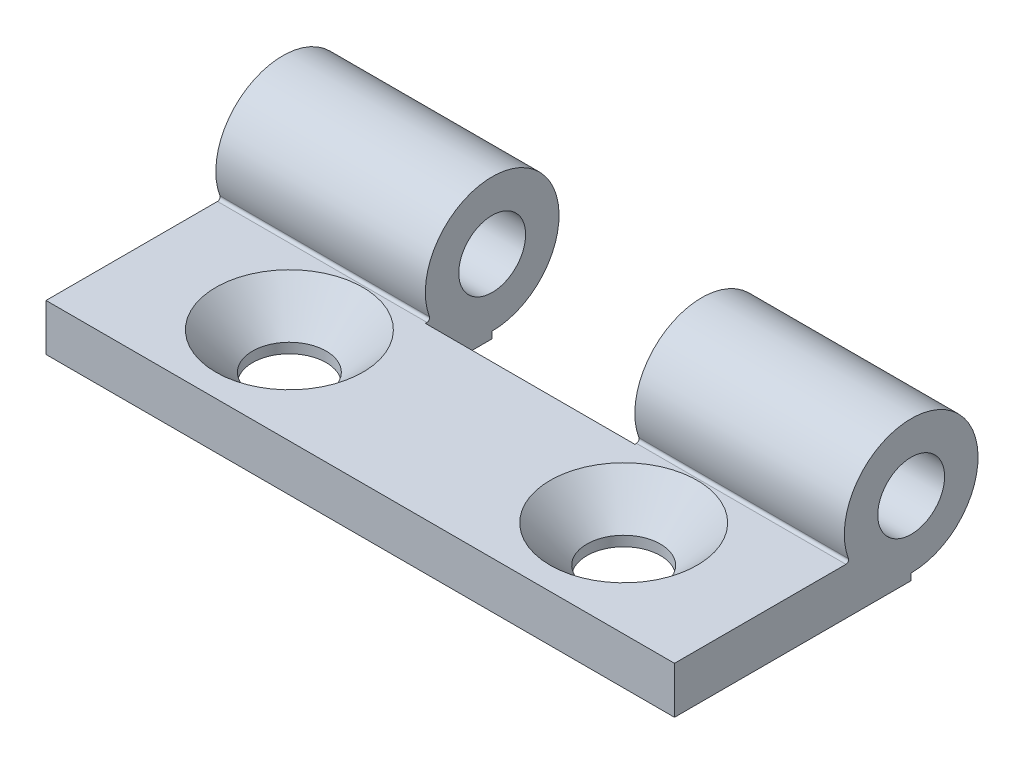
SolidWorks part; units mm, degrees
note: '?' marks a value the reader was unsure of.
ref_plane "Front Plane" through (0, 0, 0) normal (0, 0, 1) x (1, 0, 0)
ref_plane "Top Plane" through (0, 0, 0) normal (0, 1, 0) x (1, 0, 0)
ref_plane "Right Plane" through (0, 0, 0) normal (1, 0, 0) x (0, 0, -1)
ref_axis "Axis_X" through (-13.35, 0, 0) along (1, 0, 0)?
ref_axis "Axis_Y" through (0, 11.025, 0) along (0, -1, 0)?
ref_axis "Axis_Z" through (0, 0, 4.365) along (0, 0, 1)?
ref_plane "K" through (-11, 0, 0) normal (1, 0, 0) x (0, 0, -1)
ref_plane "L" through (36, 0, 0) normal (1, 0, 0) x (0, 0, -1)
sketch "Sketch1" plane through (0, 0, 0) normal (1, 0, 0) x (0, 0, -1)
  line L0 (-28.2, 0) -> (-10.5, 0)
  line L1 (-21, 3.5) -> (-21, 0) construction
  line L2 (7.2, 3.5) -> (7.2, 0) construction
  line L7 (-28.2, 3.5) -> (-15.0826, 3.5)
  line L8 (-28.2, 0) -> (-28.2, 3.5)
  line L12 (-10.5, 0.5) -> (-10.5, 0)
  circle A0 centre (-10.5, 5.5) radius 2.5
  arc A2 (-15.0826, 3.5) -> (-10.5, 0.5) centre (-10.5, 5.5) cw
  dimension "FIX_11" = 5
  dimension "R" = 5
  dimension "T" = 3.5
  dimension "KSS_2" = 17.7
  dimension "E" = 5.5
  dimension "S" = 21
  dimension "J" = 7.2
  dimension "W" = 35.4
extrude "Boss-Extrude1" add sketch "Sketch1" along normal up to surface (36 mm away) and the other way up to surface (11 mm away) up to plane "L" other way up to plane "K"
fillet "Fillet1" radius 0.2 1 edges at (12.5, 3.5, 15.0826)
sketch "Sketch2" plane through (0, 0, 0) normal (0, 1, 0) x (1, 0, 0)
  line L0 (-11, -15.3785) -> (-11, -28.2) construction
  line L1 (4.6667, -5.5) -> (20.3333, -5.5)
  line L2 (4.6667, -5.5) -> (4.6667, -15.5)
  line L3 (4.6667, -15.5) -> (20.3333, -15.5)
  line L4 (20.3333, -5.5) -> (20.3333, -15.5)
  line L6 (36, -5.5) -> (51.6667, -5.5)
  line L7 (36, -5.5) -> (36, -15.5)
  line L8 (36, -15.5) -> (51.6667, -15.5)
  line L9 (51.6667, -5.5) -> (51.6667, -15.5)
  dimension "KSS_3" = 10
  dimension "KSS_4" = 5
  dimension "KSS_11" = 15.6667
  dimension "KSS_12" = 15.6667
  dimension "KSS_10" = 15.6667
extrude "Cut-Extrude1" cut sketch "Sketch2" along normal through all
hole_wizard "CSK1" positions "Sketch4" profile "Sketch3" countersink size "M5" standard "JIS" end condition through all
sketch "Sketch4" plane through (0, 3.5, 0) normal (0, 1, 0) x (1, 0, 0)
  line L0 (0, -28.2) -> (0, -15.0826) construction
  line L1 (0, -28.2) -> (0, -10.5) construction
  point P0 (0, -21)
  point P11 (25, -21)
  dimension "P" = 25
sketch "Sketch3" plane through (0, 3.5, 21) normal (1, 0, 0) x (0, 0, 1)
  line L0 (0, 0) -> (0, 3.5001)
  line L1 (0, 3.5001) -> (2.75, 3.5001)
  line L2 (2.75, 3.5001) -> (2.75, 2.75)
  line L3 (2.75, 2.75) -> (5.5, 0)
  line L5 (5.5, 0) -> (0, 0)
  line L6 (-2.75, 2.75) -> (-5.5, 0) construction
  line L11 (0, -6.35) -> (0, 107.95) construction
  dimension "N_2" = 5.5
  dimension "Thru Hole Depth" = 3.5001
  dimension "N_1" = 11
  dimension "Near C'Sink Angle" = 90
hole_wizard "CSK2" [suppressed] positions "Sketch6" profile "Sketch5" countersink size "M5" standard "JIS"
sketch "Sketch6" plane through (0, 3.5, 0) normal (0, 1, 0) x (1, 0, 0)
  line L7 (25, -15.5) -> (25, -28.2) construction
  line L9 (36, -28.2) -> (-11, -28.2) construction
  point P0 (0, -21)
  point P2 (25, -21)
  point P4 (50, -21)
  dimension "P" = 25
sketch "Sketch5" plane through (0, 3.5, 21) normal (1, 0, 0) x (0, 0, 1)
  line L0 (0, 0) -> (0, 5.1524)
  line L1 (0, 5.1524) -> (2.75, 3.5)
  line L2 (2.75, 3.5) -> (2.75, 2.75)
  line L3 (2.75, 2.75) -> (5.5, 0)
  line L5 (5.5, 0) -> (0, 0)
  line L6 (-2.75, 2.75) -> (-5.5, 0) construction
  line L10 (0, 5.1524) -> (-2.75, 3.5) construction
  line L11 (0, -6.35) -> (0, 107.95) construction
  dimension "N_2" = 5.5
  dimension "Hole Depth" = 3.5
  dimension "N_1" = 11
  dimension "Near C'Sink Angle" = 90
  dimension "Drill Angle" = 118
equation "\"Factor\"= 1.082532"
equation "\"W\"=35.4"
equation "\"KSS_2@Sketch1\"=\"W@Sketch1\"/2"
equation "\"KSS_3\"= if ( \"W\" = 35.4 , 10 , 11 )"
equation "\"KSS_4\"= if ( \"W\" = 35.4 , 5 , 5.5 )"
equation "\"KSS_10@Sketch2\" = \"L@L\" / 3'/3"
equation "\"KSS_11@Sketch2\"= \"KSS_10@Sketch2\""
equation "\"KSS_12@Sketch2\"= \"KSS_10@Sketch2\""
